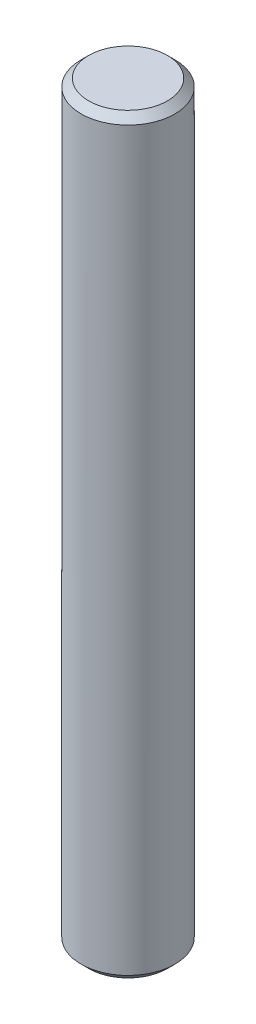
SolidWorks part; units mm, degrees
material "AISI 303 Stainless"
ref_plane "Front Plane" through (0, 0, 0) normal (0, 0, 1) x (1, 0, 0)
ref_plane "Top Plane" through (0, 0, 0) normal (0, 1, 0) x (1, 0, 0)
ref_plane "Right Plane" through (0, 0, 0) normal (1, 0, 0) x (0, 0, -1)
other "Configuration Table"
sketch "Sketch1" plane through (0, 0, 0) normal (0, 0, 1) x (1, 0, 0)
  line L0 (3.1712, 50.8) -> (0, 50.8)
  line L1 (0, 50.8) -> (0, 0)
  line L2 (0, 0) -> (3.1712, 0)
  line L3 (3.1712, 0) -> (3.1712, 50.8)
  line L4 (0, 50.8) -> (0, 0) construction
revolve "Revolve1" add sketch "Sketch1" angle 360 about L4 reverse direction yes
chamfer "Chamfer1" distance 0.508 angle 45 1 edges at (0, 0, -3.1712)
chamfer "Chamfer2" distance 0.508 angle 45 1 edges at (0, 50.8, -3.1712)
ref_point "Point2"
